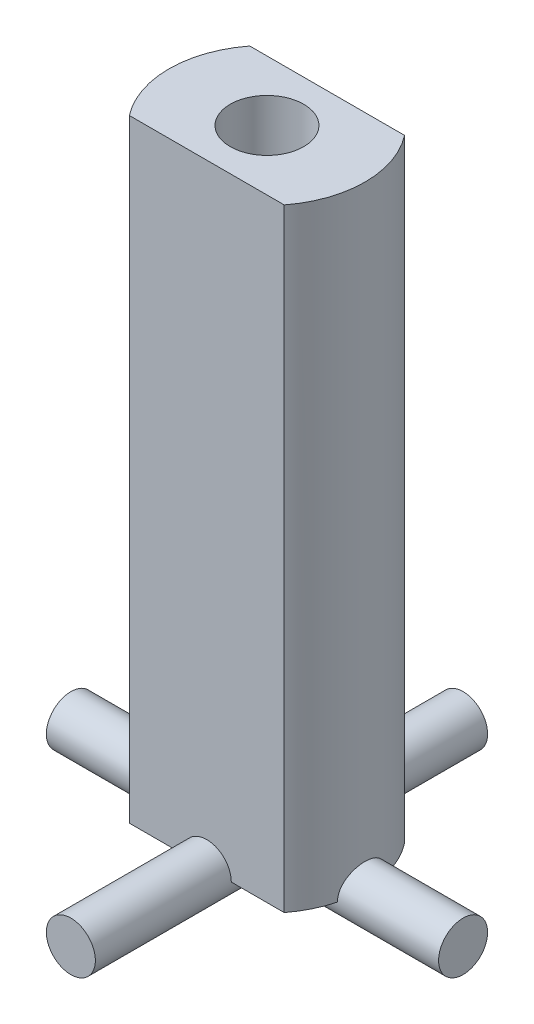
SolidWorks part; units mm, degrees
ref_plane "Front Plane" through (0, 0, 0) normal (0, 0, 1) x (1, 0, 0)
ref_plane "Top Plane" through (0, 0, 0) normal (0, 1, 0) x (1, 0, 0)
ref_plane "Right Plane" through (0, 0, 0) normal (1, 0, 0) x (0, 0, -1)
sketch "Sketch1" plane through (0, 0, 0) normal (0, 1, 0) x (1, 0, 0)
  line L0 (-1.5788, 1.2277) -> (1.5788, 1.2277)
  line L1 (-1.5788, -1.2277) -> (1.5788, -1.2277)
  arc A0 (-1.5788, 1.2277) -> (-1.5788, -1.2277) centre (0, 0) ccw
  arc A1 (1.5788, -1.2277) -> (1.5788, 1.2277) centre (0, 0) ccw
  point P7 (0, 0)
  dimension "D1" = 4
  dimension "D2" = 2.4555
extrude "Boss-Extrude1" add sketch "Sketch1" along normal blind 12.5
sketch "Sketch2" plane through (0, 12.5, 0) normal (0, 1, 0) x (1, 0, 0)
  circle A0 centre (0, 0) radius 0.75
  dimension "D1" = 1.5
extrude "Cut-Extrude1" cut sketch "Sketch2" against normal blind 4
sketch "Sketch3" plane through (0, 0, 0) normal (0, 0, 1) x (1, 0, 0)
  circle A0 centre (0, 0) radius 0.5
  dimension "D1" = 1
extrude "Boss-Extrude2" add sketch "Sketch3" along normal blind 4 and the other way blind 4
sketch "Sketch4" plane through (0, 0, 0) normal (1, 0, 0) x (0, 0, -1)
  circle A0 centre (0, 0) radius 0.5
  dimension "D1" = 1
extrude "Boss-Extrude3" add sketch "Sketch4" along normal blind 4 and the other way blind 4
